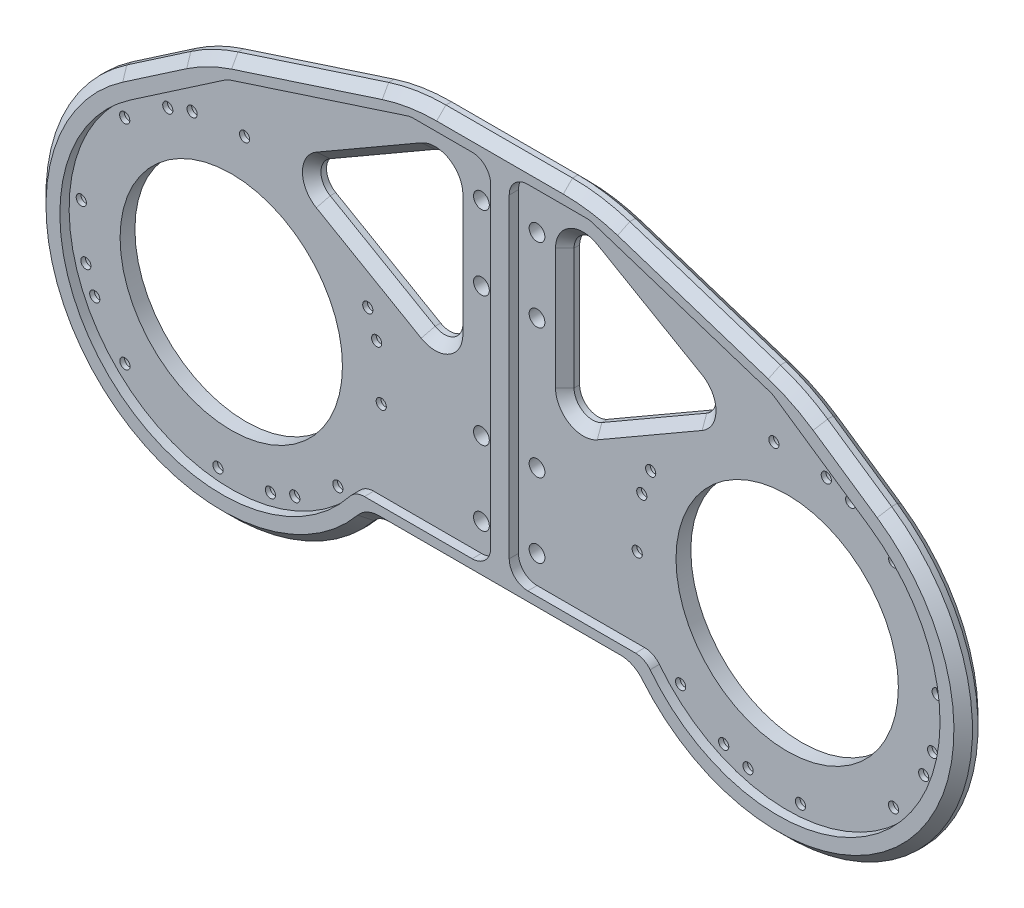
SolidWorks part; units mm, degrees
material "6061 合金"
ref_plane "前视基准面" through (0, 0, 0) normal (0, 0, 1) x (1, 0, 0)
ref_plane "上视基准面" through (0, 0, 0) normal (0, 1, 0) x (1, 0, 0)
ref_plane "右视基准面" through (0, 0, 0) normal (1, 0, 0) x (0, 0, -1)
other "Configuration Table"
sketch "草图1" plane through (0, 0, 0) normal (0, 0, 1) x (1, 0, 0)
  line L0 (0, 0) -> (0, 250) construction
  line L1 (0, 250) -> (769.4209, 0)
  line L3 (769.4209, 0) -> (0, 0)
  line L4 (-50, 352.899) -> (-50, -139.8009) construction
  line L5 (-869.4209, 0) -> (-100, 0)
  line L6 (-100, 250) -> (-869.4209, 0)
  line L7 (-100, 0) -> (-100, 250) construction
  line L8 (-100, 250) -> (0, 250)
  line L9 (0, 0) -> (-100, 0)
  circle A0 centre (100, 100) radius 85 construction
  circle A1 centre (100, 100) radius 60
  circle A2 centre (-200, 100) radius 85 construction
  circle A3 centre (-200, 100) radius 60
  dimension "D1" = 170
  dimension "D4" = 120
  dimension "D2" = 150
  dimension "D3" = 72
  dimension "D5" = 250
  dimension "D6" = 100
  dimension "D7" = 50
extrude "凸台-拉伸1" add sketch "草图1" along normal blind 8 contours L9 L3 L1 L8 L6 L5 A1 A3 region at (-50, 86.7466, 0)
sketch "草图4" plane through (0, 0, 8) normal (0, 0, 1) x (1, 0, 0)
  line L0 (-50, 330.4726) -> (-50, -61.6586) construction
  arc A0 (259.7806, 158.4465) -> (255.249, 156.3335) centre (257.5148, 157.39) ccw construction
  arc A1 (278.6673, 106.1128) -> (283.1989, 108.2258) centre (280.9331, 107.1693) ccw construction
  arc A2 (276.1928, 77.8292) -> (280.7244, 79.9423) centre (278.4586, 78.8857) ccw construction
  arc A3 (271.409, 64.6857) -> (275.9405, 66.7988) centre (273.6748, 65.7423) ccw construction
  arc A4 (255.1242, 41.4287) -> (259.6558, 43.5418) centre (257.39, 42.4852) ccw construction
  arc A5 (204.9035, 18.0104) -> (209.4351, 20.1235) centre (207.1693, 19.0669) ccw construction
  arc A6 (176.62, 20.4849) -> (181.1515, 22.598) centre (178.8857, 21.5414) ccw construction
  arc A7 (163.4765, 25.2687) -> (168.008, 27.3818) centre (165.7423, 26.3252) ccw construction
  arc A8 (140.2194, 41.5535) -> (144.751, 43.6665) centre (142.4852, 42.61) ccw construction
  arc A9 (121.3327, 93.8872) -> (116.8011, 91.7742) centre (119.0669, 92.8307) ccw construction
  arc A10 (123.8072, 122.1708) -> (119.2756, 120.0577) centre (121.5414, 121.1143) ccw construction
  arc A11 (128.591, 135.3143) -> (124.0595, 133.2012) centre (126.3252, 134.2577) ccw construction
  arc A12 (144.8758, 158.5713) -> (140.3442, 156.4582) centre (142.61, 157.5148) ccw construction
  arc A13 (195.0965, 181.9896) -> (190.5649, 179.8765) centre (192.8307, 180.9331) ccw construction
  arc A14 (223.38, 179.5151) -> (218.8485, 177.402) centre (221.1143, 178.4586) ccw construction
  arc A15 (236.5235, 174.7313) -> (231.992, 172.6182) centre (234.2577, 173.6748) ccw construction
  arc A16 (259.7806, 158.4465) -> (255.249, 156.3335) centre (257.5148, 157.39) ccw construction
  arc A17 (278.6673, 106.1128) -> (283.1989, 108.2258) centre (280.9331, 107.1693) ccw construction
  arc A18 (276.1928, 77.8292) -> (280.7244, 79.9423) centre (278.4586, 78.8857) ccw construction
  arc A19 (271.409, 64.6857) -> (275.9405, 66.7988) centre (273.6748, 65.7423) ccw construction
  arc A20 (255.1242, 41.4287) -> (259.6558, 43.5418) centre (257.39, 42.4852) ccw construction
  arc A21 (204.9035, 18.0104) -> (209.4351, 20.1235) centre (207.1693, 19.0669) ccw construction
  arc A22 (176.62, 20.4849) -> (181.1515, 22.598) centre (178.8857, 21.5414) ccw construction
  arc A23 (163.4765, 25.2687) -> (168.008, 27.3818) centre (165.7423, 26.3252) ccw construction
  arc A24 (140.2194, 41.5535) -> (144.751, 43.6665) centre (142.4852, 42.61) ccw construction
  arc A25 (121.3327, 93.8872) -> (116.8011, 91.7742) centre (119.0669, 92.8307) ccw construction
  arc A26 (123.8072, 122.1708) -> (119.2756, 120.0577) centre (121.5414, 121.1143) ccw construction
  arc A27 (128.591, 135.3143) -> (124.0595, 133.2012) centre (126.3252, 134.2577) ccw construction
  arc A28 (144.8758, 158.5713) -> (140.3442, 156.4582) centre (142.61, 157.5148) ccw construction
  arc A29 (195.0965, 181.9896) -> (190.5649, 179.8765) centre (192.8307, 180.9331) ccw construction
  arc A30 (223.38, 179.5151) -> (218.8485, 177.402) centre (221.1143, 178.4586) ccw construction
  arc A31 (236.5235, 174.7313) -> (231.992, 172.6182) centre (234.2577, 173.6748) ccw construction
  circle A32 centre (257.5148, 157.39) radius 2.75
  circle A33 centre (234.2577, 173.6748) radius 2.75
  circle A34 centre (221.1143, 178.4586) radius 2.75
  circle A35 centre (192.8307, 180.9331) radius 2.75
  circle A36 centre (142.61, 157.5148) radius 2.75
  circle A37 centre (126.3252, 134.2577) radius 2.75
  circle A38 centre (121.5414, 121.1143) radius 2.75
  circle A39 centre (119.0669, 92.8307) radius 2.75
  circle A40 centre (142.4852, 42.61) radius 2.75
  circle A41 centre (165.7423, 26.3252) radius 2.75
  circle A42 centre (178.8857, 21.5414) radius 2.75
  circle A43 centre (207.1693, 19.0669) radius 2.75
  circle A44 centre (257.39, 42.4852) radius 2.75
  circle A45 centre (273.6748, 65.7423) radius 2.75
  circle A46 centre (278.4586, 78.8857) radius 2.75
  circle A47 centre (280.9331, 107.1693) radius 2.75
  circle A48 centre (100, 100) radius 60 construction
  circle A49 centre (-200, 100) radius 60 construction
  arc A50 (-336.5235, 174.7313) -> (-331.992, 172.6182) centre (-334.2577, 173.6748) cw construction
  arc A51 (-323.38, 179.5151) -> (-318.8485, 177.402) centre (-321.1143, 178.4586) cw construction
  arc A52 (-295.0965, 181.9896) -> (-290.5649, 179.8765) centre (-292.8307, 180.9331) cw construction
  arc A53 (-244.8758, 158.5713) -> (-240.3442, 156.4582) centre (-242.61, 157.5148) cw construction
  arc A54 (-228.591, 135.3143) -> (-224.0595, 133.2012) centre (-226.3252, 134.2577) cw construction
  arc A55 (-223.8072, 122.1708) -> (-219.2756, 120.0577) centre (-221.5414, 121.1143) cw construction
  arc A56 (-221.3327, 93.8872) -> (-216.8011, 91.7742) centre (-219.0669, 92.8307) cw construction
  arc A57 (-240.2194, 41.5535) -> (-244.751, 43.6665) centre (-242.4852, 42.61) cw construction
  arc A58 (-263.4765, 25.2687) -> (-268.008, 27.3818) centre (-265.7423, 26.3252) cw construction
  arc A59 (-276.62, 20.4849) -> (-281.1515, 22.598) centre (-278.8857, 21.5414) cw construction
  arc A60 (-304.9035, 18.0104) -> (-309.4351, 20.1235) centre (-307.1693, 19.0669) cw construction
  arc A61 (-355.1242, 41.4287) -> (-359.6558, 43.5418) centre (-357.39, 42.4852) cw construction
  arc A62 (-371.409, 64.6857) -> (-375.9405, 66.7988) centre (-373.6748, 65.7423) cw construction
  arc A63 (-376.1928, 77.8292) -> (-380.7244, 79.9423) centre (-378.4586, 78.8857) cw construction
  arc A64 (-378.6673, 106.1128) -> (-383.1989, 108.2258) centre (-380.9331, 107.1693) cw construction
  arc A65 (-359.7806, 158.4465) -> (-355.249, 156.3335) centre (-357.5148, 157.39) cw construction
  circle A66 centre (-380.9331, 107.1693) radius 2.75
  circle A67 centre (-378.4586, 78.8857) radius 2.75
  circle A68 centre (-373.6748, 65.7423) radius 2.75
  circle A69 centre (-357.39, 42.4852) radius 2.75
  circle A70 centre (-307.1693, 19.0669) radius 2.75
  circle A71 centre (-278.8857, 21.5414) radius 2.75
  circle A72 centre (-265.7423, 26.3252) radius 2.75
  circle A73 centre (-242.4852, 42.61) radius 2.75
  circle A74 centre (-219.0669, 92.8307) radius 2.75
  circle A75 centre (-221.5414, 121.1143) radius 2.75
  circle A76 centre (-226.3252, 134.2577) radius 2.75
  circle A77 centre (-242.61, 157.5148) radius 2.75
  circle A78 centre (-292.8307, 180.9331) radius 2.75
  circle A79 centre (-321.1143, 178.4586) radius 2.75
  circle A80 centre (-334.2577, 173.6748) radius 2.75
  circle A81 centre (-357.5148, 157.39) radius 2.75
  dimension "D1" = 5.5
extrude "切除-拉伸2" [suppressed] cut sketch "草图4" against normal blind 10 contours A44 | A45 | A46 | A47 | A32 | A33 | A34 | A35 | A36 | A37 | A38 | A39 | A40 | A41 | A42 | A73 | A72 | A71 | A70 | A69 | A68 | A67 | A66 | A81 | A80 | A79 | A78 | A77 | A76 | A75 | A74 | A43
sketch "草图5" plane through (0, 0, 0) normal (0, 0, -1) x (-1, 0, 0)
  line L0 (50, 354.5789) -> (50, -118.9875) construction
  circle A16 centre (200, 100) radius 60 construction
  circle A17 centre (-100, 100) radius 60 construction
extrude "切除-拉伸3" [suppressed] cut sketch "草图5" against normal blind 5.5
fillet "圆角1" radius 100 2 edges at (-869.4209, 0, 4) (769.4209, 0, 4)
sketch "草图6" plane through (0, 0, 8) normal (0, 0, 1) x (1, 0, 0)
  line L0 (-50, 293.5967) -> (-50, -68.7433) construction
  line L1 (-120, 40) -> (20, 40)
  line L2 (138.0457, 0) -> (-238.0457, 0) construction
  line L3 (100, 0) -> (-200, 0)
  circle A0 centre (100, 100) radius 85.25 construction
  arc A1 (20, 40) -> (100, 0) centre (100, 100) ccw
  circle A2 centre (100, 100) radius 60 construction
  circle A3 centre (-200, 100) radius 60 construction
  arc A4 (-120, 40) -> (-200, 0) centre (-200, 100) cw
  dimension "D1" = 170.5
  dimension "D2" = 200
  dimension "D3" = 40
extrude "切除-拉伸4" cut sketch "草图6" against normal blind 10
sketch "草图7" plane through (0, 0, 8) normal (0, 0, 1) x (1, 0, 0)
  line L0 (-50, 316.0763) -> (-50, -100.7481) construction
  line L1 (-200, 0) -> (-238.0457, 0) construction
  line L2 (-256.3883, 182.5854) -> (-210, 214.2588)
  line L3 (-100, 250) -> (-268.9474, 195.1057) construction
  line L4 (-200, 0) -> (-238.0457, 0)
  line L5 (-210, 214.2588) -> (-268.9474, 195.1057)
  line L6 (110, 214.2588) -> (168.9474, 195.1057)
  line L7 (100, 0) -> (138.0457, 0)
  line L8 (156.3883, 182.5854) -> (110, 214.2588)
  arc A0 (-256.3883, 182.5854) -> (-200, 0) centre (-200, 100) ccw
  circle A1 centre (100, 100) radius 60 construction
  circle A2 centre (-200, 100) radius 60 construction
  arc A3 (-268.9474, 195.1057) -> (-238.0457, 0) centre (-238.0457, 100) ccw construction
  arc A4 (-268.9474, 195.1057) -> (-238.0457, 0) centre (-238.0457, 100) ccw
  arc A5 (168.9474, 195.1057) -> (138.0457, 0) centre (138.0457, 100) cw
  arc A6 (156.3883, 182.5854) -> (100, 0) centre (100, 100) cw
  point P15 (-282.4158, 178.5318)
  dimension "D1" = 160
extrude "切除-拉伸5" cut sketch "草图7" against normal blind 83
fillet "圆角2" radius 10 2 edges at (20, 40, 4) (-120, 40, 4)
fillet "圆角3" radius 100 4 edges at (110, 214.2588, 4) (0, 250, 4) (-100, 250, 4) (-210, 214.2588, 4)
sketch "草图8" plane through (0, 0, 8) normal (0, 0, 1) x (1, 0, 0)
  line L0 (-50, 283.5634) -> (-50, -10.7461) construction
  line L1 (15.1472, 40) -> (-115.1472, 40) construction
  circle A0 centre (-200, 100) radius 60 construction
  circle A1 centre (100, 100) radius 60 construction
  circle A2 centre (-35, 65) radius 4.25
  circle A3 centre (-35, 105) radius 4.25
  circle A4 centre (-35, 175) radius 4.25
  circle A5 centre (-35, 215) radius 4.25
  circle A6 centre (-65, 215) radius 4.25
  circle A7 centre (-65, 175) radius 4.25
  circle A8 centre (-65, 105) radius 4.25
  circle A9 centre (-65, 65) radius 4.25
  point P14 (0, 0)
  dimension "D1" = 8.5
  dimension "D2" = 25
  dimension "D3" = 40
  dimension "D4" = 40
  dimension "D5" = 70
  dimension "D6" = 15
extrude "切除-拉伸6" cut sketch "草图8" against normal blind 10
sketch "草图9" plane through (0, 0, 8) normal (0, 0, 1) x (1, 0, 0)
  line L0 (-50, 299.1056) -> (-50, -13.7223) construction
  line L1 (-45, 50) -> (28.193, 50)
  line L2 (-45, 240) -> (-1.5838, 240)
  line L3 (-1.5838, 240) -> (97.0868, 207.94)
  line L4 (97.0868, 207.94) -> (149.3398, 172.2623)
  line L5 (15.1472, 40) -> (-115.1472, 40) construction
  line L6 (-84.1616, 250) -> (-15.8384, 250) construction
  line L7 (15.0633, 245.1057) -> (96.3588, 218.6911) construction
  line L8 (121.8454, 206.1709) -> (156.3883, 182.5854) construction
  line L9 (-45, 240) -> (-45, 50)
  line L10 (-55, 240) -> (-55, 50)
  line L11 (-197.0868, 207.94) -> (-249.3398, 172.2623)
  line L12 (-98.4162, 240) -> (-197.0868, 207.94)
  line L13 (-55, 240) -> (-98.4162, 240)
  line L14 (-55, 50) -> (-128.193, 50)
  line L21 (156.3883, 182.5854) -> (121.8454, 206.1709)
  line L22 (96.3588, 218.6911) -> (15.0633, 245.1057)
  line L23 (-15.8384, 250) -> (-84.1616, 250)
  line L24 (-115.0633, 245.1057) -> (-196.3588, 218.6911)
  line L25 (-221.8454, 206.1709) -> (-256.3883, 182.5854)
  line L26 (-115.1472, 40) -> (15.1472, 40)
  line L27 (156.3883, 182.5854) -> (121.8454, 206.1709)
  line L28 (96.3588, 218.6911) -> (15.0633, 245.1057)
  line L29 (-15.8384, 250) -> (-84.1616, 250)
  line L30 (-115.0633, 245.1057) -> (-196.3588, 218.6911)
  line L31 (-221.8454, 206.1709) -> (-256.3883, 182.5854)
  line L32 (-115.1472, 40) -> (15.1472, 40)
  circle A0 centre (100, 100) radius 87.5 construction
  circle A1 centre (100, 100) radius 60 construction
  circle A2 centre (-200, 100) radius 60 construction
  arc A3 (28.193, 50) -> (149.3398, 172.2623) centre (100, 100) ccw
  circle A4 centre (-200, 100) radius 87.5 construction
  arc A5 (-128.193, 50) -> (-249.3398, 172.2623) centre (-200, 100) cw
  arc A14 (121.8454, 206.1709) -> (96.3588, 218.6911) centre (65.4571, 123.5855) ccw
  arc A15 (15.0633, 245.1057) -> (-15.8384, 250) centre (-15.8384, 150) ccw
  arc A16 (-84.1616, 250) -> (-115.0633, 245.1057) centre (-84.1616, 150) ccw
  arc A17 (-196.3588, 218.6911) -> (-221.8454, 206.1709) centre (-165.4571, 123.5855) ccw
  arc A18 (-256.3883, 182.5854) -> (-122.8611, 36.3636) centre (-200, 100) ccw
  arc A19 (-115.1472, 40) -> (-122.8611, 36.3636) centre (-115.1472, 30) ccw
  arc A20 (22.8611, 36.3636) -> (15.1472, 40) centre (15.1472, 30) ccw
  arc A21 (22.8611, 36.3636) -> (156.3883, 182.5854) centre (100, 100) ccw
  arc A22 (121.8454, 206.1709) -> (96.3588, 218.6911) centre (65.4571, 123.5855) ccw
  arc A23 (15.0633, 245.1057) -> (-15.8384, 250) centre (-15.8384, 150) ccw
  arc A24 (-84.1616, 250) -> (-115.0633, 245.1057) centre (-84.1616, 150) ccw
  arc A25 (-196.3588, 218.6911) -> (-221.8454, 206.1709) centre (-165.4571, 123.5855) ccw
  arc A26 (-256.3883, 182.5854) -> (-122.8611, 36.3636) centre (-200, 100) ccw
  arc A27 (-115.1472, 40) -> (-122.8611, 36.3636) centre (-115.1472, 30) ccw
  arc A28 (22.8611, 36.3636) -> (15.1472, 40) centre (15.1472, 30) ccw
  arc A29 (22.8611, 36.3636) -> (156.3883, 182.5854) centre (100, 100) ccw
  dimension "D1" = 175
  dimension "D2" = 10
  dimension "D3" = 10
  dimension "D4" = 10
  dimension "D5" = 5
  dimension "D6" = 0
extrude "凸台-拉伸2" add sketch "草图9" along normal blind 5
sketch "草图10" plane through (0, 0, 8) normal (0, 0, 1) x (1, 0, 0)
  line L0 (-20, 230) -> (-20, 130)
  line L1 (-20, 130) -> (66.6025, 180)
  line L2 (66.6025, 180) -> (-20, 230)
  line L3 (-50, 285.8782) -> (-50, -42.8226) construction
  line L4 (-15.8384, 250) -> (-84.1616, 250) construction
  line L5 (-166.6025, 180) -> (-80, 230)
  line L6 (-80, 130) -> (-166.6025, 180)
  line L7 (-80, 230) -> (-80, 130)
  circle A0 centre (100, 100) radius 60 construction
  circle A1 centre (-200, 100) radius 60 construction
  point P11 (83.9274, 189.9796)
  point P12 (81.6126, 182.3738)
  dimension "D1" = 30
  dimension "D2" = 20
  dimension "D3" = 100
  dimension "D4" = 100
  dimension "D5" = 100
extrude "切除-拉伸7" cut sketch "草图10" against normal blind 94
fillet "圆角4" radius 10 16 edges at (-166.6025, 180, 4) (-80, 230, 4) (-80, 130, 4) (-20, 130, 4) (-20, 230, 4) (66.6025, 180, 4) (97.0868, 207.94, 10.5) (28.193, 50, 10.5) (-1.5838, 240, 10.5) (-45, 240, 10.5) (-45, 50, 10.5) (-55, 50, 10.5) (-128.193, 50, 10.5) (-197.0868, 207.94, 10.5) (-98.4162, 240, 10.5) (-55, 240, 10.5)
chamfer "倒角1" distance 5 angle 45 40 edges at (-156.6025, 180, 8) (-123.3013, 155, 8) (-123.3013, 205, 8) (-85, 138.6603, 8) (-85, 221.3397, 8) (-80, 180, 8) (56.6025, 180, 8) (23.3013, 205, 8) (23.3013, 155, 8) (-15, 221.3397, 8) (-15, 138.6603, 8) (-20, 180, 8) (55.711, 231.8984, 0) (109.5488, 213.3403, 0) (-0.195, 248.7688, 0) (139.1169, 194.3782, 0) (-50, 250, 0) (173.8434, 32.5674, 0) (-99.805, 248.7688, 0) (19.4112, 39.0453, 0) (-155.711, 231.8984, 0) (-50, 40, 0) (-209.5488, 213.3403, 0) (-119.4112, 39.0453, 0) (-239.1169, 194.3782, 0) (-273.8434, 32.5674, 0) (109.5488, 213.3403, 13) (55.711, 231.8984, 13) (139.1169, 194.3782, 13) (-0.195, 248.7688, 13) (173.8434, 32.5674, 13) (-50, 250, 13) (19.4112, 39.0453, 13) (-99.805, 248.7688, 13) (-50, 40, 13) (-155.711, 231.8984, 13) (-119.4112, 39.0453, 13) (-209.5488, 213.3403, 13) (-273.8434, 32.5674, 13) (-239.1169, 194.3782, 13)
sketch "草图15" plane through (0, 0, 8) normal (0, 0, 1) x (1, 0, 0)
  line L0 (100, 100) -> (91.5104, 195.8805) construction
  line L1 (100, 100) -> (124.8065, 192.1927) construction
  line L2 (100, 100) -> (137.0586, 179.6901) construction
  line L3 (100, 100) -> (151.313, 151.2057) construction
  line L4 (-45, 230) -> (-45, 60) construction
  line L5 (-50, 286.5396) -> (-50, -57.042) construction
  line L6 (-200, 100) -> (-251.313, 151.2057) construction
  line L7 (-200, 100) -> (-237.0586, 179.6901) construction
  line L8 (-200, 100) -> (-224.8065, 192.1927) construction
  line L9 (-200, 100) -> (-191.5104, 195.8805) construction
  circle A0 centre (92.8338, 180.9334) radius 2.75
  circle A1 centre (121.1112, 178.4594) radius 2.75
  circle A2 centre (134.2606, 173.6734) radius 2.75
  circle A3 centre (157.5126, 157.3922) radius 2.75
  circle A4 centre (157.3922, 42.4874) radius 2.75
  circle A5 centre (173.6734, 65.7394) radius 2.75
  circle A6 centre (178.4594, 78.8888) radius 2.75
  circle A7 centre (180.9334, 107.1662) radius 2.75
  circle A8 centre (42.4874, 42.6078) radius 2.75
  circle A9 centre (65.7394, 26.3266) radius 2.75
  circle A10 centre (78.8888, 21.5406) radius 2.75
  circle A11 centre (107.1662, 19.0666) radius 2.75
  circle A12 centre (42.6078, 157.5126) radius 2.75 construction
  circle A13 centre (26.3266, 134.2606) radius 2.75
  circle A14 centre (21.5406, 121.1112) radius 2.75
  circle A15 centre (19.0666, 92.8338) radius 2.75
  circle A16 centre (100, 100) radius 60 construction
  circle A17 centre (-200, 100) radius 60 construction
  circle A18 centre (-119.0666, 92.8338) radius 2.75
  circle A19 centre (-121.5406, 121.1112) radius 2.75
  circle A20 centre (-126.3266, 134.2606) radius 2.75
  circle A21 centre (-142.6078, 157.5126) radius 2.75 construction
  circle A22 centre (-207.1662, 19.0666) radius 2.75
  circle A23 centre (-178.8888, 21.5406) radius 2.75
  circle A24 centre (-165.7394, 26.3266) radius 2.75
  circle A25 centre (-142.4874, 42.6078) radius 2.75
  circle A26 centre (-280.9334, 107.1662) radius 2.75
  circle A27 centre (-278.4594, 78.8888) radius 2.75
  circle A28 centre (-273.6734, 65.7394) radius 2.75
  circle A29 centre (-257.3922, 42.4874) radius 2.75
  circle A30 centre (-257.5126, 157.3922) radius 2.75
  circle A31 centre (-234.2606, 173.6734) radius 2.75
  circle A32 centre (-221.1112, 178.4594) radius 2.75
  circle A33 centre (-192.8338, 180.9334) radius 2.75
  point P43 (100, 100)
  point P84 (-200, 100)
  dimension "D9" = 5.5
  dimension "D1" = 5.06
  dimension "D2" = 30
  dimension "D3" = 30
  dimension "D4" = 50.12
  dimension "D5" = 81.25
  dimension "D6" = 81.25
  dimension "D7" = 81.25
  dimension "D8" = 81.25
  dimension "D10" = 4
extrude "切除-拉伸8" cut sketch "草图15" against normal blind 48.5
sketch "草图16" plane through (0, 0, 0) normal (0, 0, -1) x (-1, 0, 0)
  line L0 (50, 280.5872) -> (50, -6.4472) construction
  circle A0 centre (200, 100) radius 60 construction
  circle A1 centre (-100, 100) radius 60 construction
  circle A2 centre (192.8338, 180.9334) radius 6
  circle A3 centre (221.1112, 178.4594) radius 6
  circle A4 centre (234.2606, 173.6734) radius 6
  circle A5 centre (257.5126, 157.3922) radius 6
  circle A6 centre (280.9334, 107.1662) radius 6
  circle A7 centre (278.4594, 78.8888) radius 6
  circle A8 centre (273.6734, 65.7394) radius 6
  circle A9 centre (257.3922, 42.4874) radius 6
  circle A10 centre (207.1662, 19.0666) radius 6
  circle A11 centre (178.8888, 21.5406) radius 6
  circle A12 centre (165.7394, 26.3266) radius 6
  circle A13 centre (142.4874, 42.6078) radius 6
  circle A14 centre (119.0666, 92.8338) radius 6
  circle A15 centre (121.5406, 121.1112) radius 6
  circle A16 centre (126.3266, 134.2606) radius 6
  circle A19 centre (-26.3266, 134.2606) radius 6
  circle A20 centre (-21.5406, 121.1112) radius 6
  circle A21 centre (-19.0666, 92.8338) radius 6
  circle A22 centre (-42.4874, 42.6078) radius 6
  circle A23 centre (-65.7394, 26.3266) radius 6
  circle A24 centre (-78.8888, 21.5406) radius 6
  circle A25 centre (-107.1662, 19.0666) radius 6
  circle A26 centre (-157.3922, 42.4874) radius 6
  circle A27 centre (-173.6734, 65.7394) radius 6
  circle A28 centre (-178.4594, 78.8888) radius 6
  circle A29 centre (-180.9334, 107.1662) radius 6
  circle A30 centre (-157.5126, 157.3922) radius 6
  circle A31 centre (-134.2606, 173.6734) radius 6
  circle A32 centre (-121.1112, 178.4594) radius 6
  circle A33 centre (-92.8338, 180.9334) radius 6
  dimension "D1" = 12
extrude "切除-拉伸10" cut sketch "草图16" against normal blind 5.5
